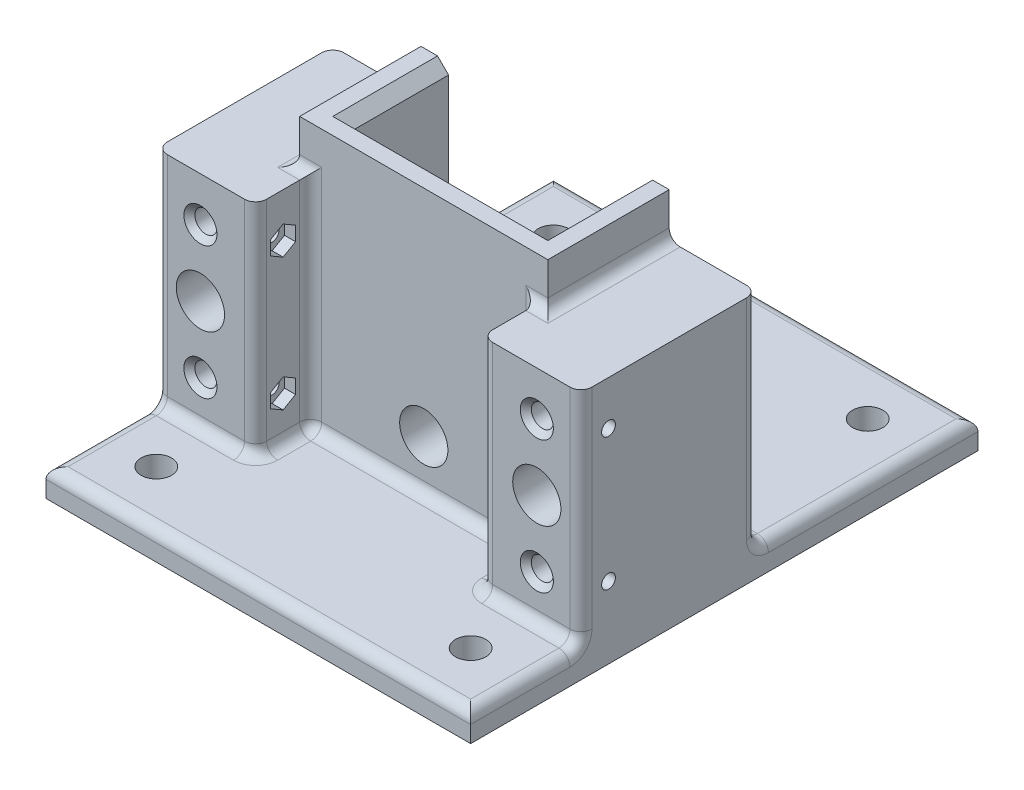
SolidWorks part; units mm, degrees
ref_plane "Спереди" through (0, 0, 0) normal (0, 0, 1) x (1, 0, 0)
ref_plane "Сверху" through (0, 0, 0) normal (0, 1, 0) x (1, 0, 0)
ref_plane "Справа" through (0, 0, 0) normal (1, 0, 0) x (0, 0, -1)
sketch "Эскиз1" plane through (0, 0, 0) normal (0, 1, 0) x (1, 0, 0)
  line L0 (0, 0) -> (0, 22)
  line L1 (0, 0) -> (45, 0)
  line L2 (22.5, 0) -> (22.5, 22) construction
  line L3 (5, 22) -> (40, 22) construction
  line L4 (0, 22) -> (5, 22)
  line L5 (5, 22) -> (5, 5)
  line L6 (5, 5) -> (40, 5)
  line L7 (40, 22) -> (40, 5)
  line L8 (45, 22) -> (40, 22)
  line L9 (45, 0) -> (45, 22)
  point P7 (22.5, 5)
  dimension "D1" = 5
  dimension "D2" = 17.5
  dimension "D3" = 17
  dimension "D4" = 5
extrude "Бобышка-Вытянуть1" add sketch "Эскиз1" along normal blind 30
sketch "Эскиз2" plane through (45, 0, 0) normal (1, 0, 0) x (0, 0, -1)
  line L0 (0, 22) -> (-10, 22)
  line L1 (0, 22) -> (0, -18)
  line L2 (-10, 22) -> (-10, -18)
  line L3 (0, -18) -> (-10, -18)
  line L4 (0, 30) -> (0, 0) construction
  line L5 (0, 30) -> (22, 30) construction
  dimension "D1" = 10
  dimension "D2" = 8
  dimension "D3" = 40
extrude "Бобышка-Вытянуть2" add sketch "Эскиз2" against normal blind 2
sketch "Эскиз3" plane through (45, 0, 0) normal (1, 0, 0) x (0, 0, -1)
  line L0 (0, 22) -> (-10, 22) construction
  line L1 (-10, 22) -> (-10, -18) construction
  line L2 (22, 22) -> (-10, 22)
  line L3 (-10, 22) -> (-10, -18)
  line L4 (-10, -18) -> (0, -18) construction
  line L5 (-10, -18) -> (22, -18)
  line L6 (22, 30) -> (22, 0) construction
  line L7 (22, 22) -> (22, -18)
extrude "Бобышка-Вытянуть3" add sketch "Эскиз3" along normal blind 16
sketch "Эскиз4" plane through (0, 0, -22) normal (0, 0, -1) x (-1, 0, 0)
  line L0 (-53, 22) -> (-53, -18) construction
  line L1 (-61, 22) -> (-45, 22) construction
  line L2 (-61, -18) -> (-45, -18) construction
  circle A0 centre (-53, 2) radius 4.375
  dimension "D1" = 8.75
extrude "Вырез-Вытянуть1" cut sketch "Эскиз4" against normal through all
sketch "Эскиз5" plane through (43, 0, 0) normal (-1, 0, 0) x (0, 0, 1)
  line L0 (5, 22) -> (5, -18) construction
  line L1 (0, 22) -> (10, 22) construction
  line L2 (10, -18) -> (0, -18) construction
  line L3 (5, 2) -> (10, 2) construction
  line L4 (10, 22) -> (10, -18) construction
  circle A0 centre (5, 14) radius 1.25
  circle A1 centre (5, -10) radius 1.25
  dimension "D1" = 12
  dimension "D2" = 2.5
extrude "Вырез-Вытянуть2" cut sketch "Эскиз5" against normal through all
sketch "Эскиз6" plane through (0, 0, -22) normal (0, 0, -1) x (-1, 0, 0)
  line L0 (-61, 15.25) -> (-61, 12.75) construction
  line L1 (-61, 15.25) -> (-61, 12.75) construction
  line L2 (-61, 14) -> (-40, 14) construction
  line L3 (-40, 30) -> (-40, 0) construction
  line L4 (-61, -8.75) -> (-61, -11.25) construction
  line L5 (-61, -8.75) -> (-61, -11.25) construction
  line L6 (-61, -10) -> (-40, -10) construction
  line L7 (-53, 14) -> (-53, -10) construction
  circle A0 centre (-53, 2) radius 4.375 construction
  circle A1 centre (-53, 2) radius 4.375 construction
  circle A2 centre (-53, 14) radius 2
  circle A3 centre (-53, -10) radius 2
  dimension "D1" = 4
  dimension "D2" = 4
extrude "Вырез-Вытянуть3" cut sketch "Эскиз6" against normal through all
sketch "Эскиз7" plane through (43, 0, 0) normal (-1, 0, 0) x (0, 0, 1)
  line L0 (5, 14) -> (5, 16.5981) construction
  line L1 (5, 11.4019) -> (7.25, 12.701)
  line L2 (7.25, 12.701) -> (7.25, 15.299)
  line L3 (7.25, 15.299) -> (5, 16.5981)
  line L4 (5, 16.5981) -> (2.75, 15.299)
  line L5 (2.75, 15.299) -> (2.75, 12.701)
  line L6 (2.75, 12.701) -> (5, 11.4019)
  line L7 (5, -7.4019) -> (2.75, -8.701)
  line L8 (2.75, -8.701) -> (2.75, -11.299)
  line L9 (2.75, -11.299) -> (5, -12.5981)
  line L10 (5, -12.5981) -> (7.25, -11.299)
  line L11 (7.25, -11.299) -> (7.25, -8.701)
  line L12 (7.25, -8.701) -> (5, -7.4019)
  line L13 (5, -10) -> (5, -7.4019) construction
  circle A0 centre (5, 14) radius 1.25 construction
  circle A1 centre (5, -10) radius 1.25 construction
  circle A2 centre (5, 14) radius 1.25 construction
  circle A3 centre (5, -10) radius 1.25 construction
  circle A4 centre (5, 14) radius 2.25 construction
  circle A5 centre (5, -10) radius 2.25 construction
  dimension "D1" = 4.5
  dimension "D2" = 4.5
extrude "Вырез-Вытянуть4" cut sketch "Эскиз7" against normal blind 2
chamfer "Фаска2" distance 3 angle 45 1 edges at (48.625, 2, -22)
chamfer "Фаска3" distance 1 angle 45 2 edges at (51, -10, -22) (51, 14, -22)
sketch "Эскиз8" plane through (0, 0, -5) normal (0, 0, -1) x (-1, 0, 0)
  line L0 (-22.5, 30) -> (-22.5, 0) construction
  line L1 (-40, 30) -> (-5, 30) construction
  line L2 (-40, 0) -> (-5, 0) construction
ref_plane "Sym" through (22.5, 0, 0) normal (1, 0, 0) x (0, -1, 0)
mirror "Зеркальное отражение2" about plane through (22.5, 0, 0) normal (1, 0, 0) of "Вырез-Вытянуть1", "Бобышка-Вытянуть3", "Бобышка-Вытянуть2", "Вырез-Вытянуть4", "Вырез-Вытянуть3", "Вырез-Вытянуть2"
chamfer "Фаска4" distance 3 angle 45 1 edges at (-3.625, 2, -22)
sketch "Эскиз9" plane through (0, 0, 0) normal (0, -1, 0) x (1, 0, 0)
  line L9 (2, 0) -> (0, 0)
  line L10 (2, 0) -> (0, 0)
  line L12 (0, -22) -> (5, -22)
  line L13 (5, -22) -> (5, -5)
  line L14 (5, -5) -> (40, -5)
  line L15 (40, -5) -> (40, -22)
  line L16 (40, -22) -> (45, -22)
  line L17 (45, -22) -> (45, 0)
  line L18 (45, 0) -> (43, 0)
  line L19 (43, 0) -> (2, 0)
  line L20 (0, 0) -> (0, -22)
  line L21 (0, 0) -> (0, -22)
  line L22 (0, -22) -> (45, -22)
  line L27 (45, -22) -> (45, 0)
  line L28 (45, 0) -> (43, 0)
  line L29 (43, 0) -> (2, 0)
  dimension "D1" = 0
extrude "Бобышка-Вытянуть4" add sketch "Эскиз9" along normal up to surface (18 mm away) up to face at (49.5, -18, -2.1667)
sketch "Эскиз10" plane through (0, 0, -22) normal (0, 0, -1) x (-1, 0, 0)
  line L0 (-22.5, 0) -> (-22.5, -18) construction
  line L1 (-5, 0) -> (-40, 0) construction
  line L2 (-61, -18) -> (16, -18) construction
  circle A0 centre (-22.5, -9) radius 4.375
  circle A1 centre (8, 2) radius 4.375 construction
extrude "Вырез-Вытянуть5" cut sketch "Эскиз10" against normal through all
chamfer "Фаска6" distance 3 angle 45 1 edges at (18.125, -9, -22)
sketch "Эскиз11" plane through (0, 0, 10) normal (0, 0, 1) x (1, 0, 0)
  line L0 (53, 16) -> (53, -12) construction
  circle A0 centre (53, 14) radius 2 construction
  circle A1 centre (53, -10) radius 2 construction
ref_plane "Плоскость1" through (53, 0, 0) normal (-1, 0, 0) x (0, -1, 0)
chamfer "Фаска7" distance 1 angle 45 4 edges at (-6, -10, 10) (-6, 14, 10) (51, -10, 10) (51, 14, 10)
chamfer "Фаска8" distance 2 angle 45 1 edges at (5, 30, -13.5)
fillet "Скругление3" radius 2 6 edges at (43, 2, 0) (2, 2, 0)
sketch "Эскиз12" plane through (0, -18, 0) normal (0, -1, 0) x (1, 0, 0)
  line L0 (-16, 10) -> (61, 10)
  line L1 (-16, 10) -> (-16, -62)
  line L2 (61, 10) -> (61, -62)
  line L3 (-16, -62) -> (61, -62)
  line L4 (-16, 10) -> (-16, -22) construction
  line L5 (61, 10) -> (61, -22) construction
  line L6 (61, -22) -> (-16, -22) construction
  line L8 (43, 10) -> (61, 10) construction
  dimension "D1" = 40
extrude "Бобышка-Вытянуть5" add sketch "Эскиз12" along normal blind 5
fillet "Скругление7" radius 2 1 edges
sketch "Эскиз13" plane through (0, 0, 10) normal (0, 0, 1) x (1, 0, 0)
  line L0 (-16, 22) -> (-16, -23) construction
  line L1 (61, -23) -> (-16, -23) construction
  line L2 (61, 22) -> (61, -23) construction
  line L3 (43, -18) -> (2, -18) construction
  line L4 (-16, -18) -> (-16, -23)
  line L5 (61, -23) -> (-16, -23)
  line L6 (61, -18) -> (61, -23)
  line L7 (61, -18) -> (-16, -18)
extrude "Бобышка-Вытянуть6" add sketch "Эскиз13" along normal blind 20
fillet "Скругление10" radius 2 14 edges at (2.5858, -18, 0.5858) (22.5, -18, 0) (42.4142, -18, 0.5858) (22.5, -18, 30)
fillet "Скругление11" radius 2 7 edges at (61, -17.4142, -22.5858) (-16, -17.4142, -22.5858) (22.5, -18, -62)
sketch "Эскиз14" plane through (0, -18, 0) normal (0, 1, 0) x (1, 0, 0)
  line L0 (-14, -20) -> (59, -20) construction
  line L1 (-14, -12) -> (-14, -28) construction
  line L2 (59, -28) -> (59, -12) construction
  line L3 (-14, 52) -> (59, 52) construction
  line L4 (-14, 60) -> (-14, 24) construction
  line L5 (59, 24) -> (59, 60) construction
  line L6 (61, -30) -> (-16, -30) construction
  line L8 (-16, 62) -> (61, 62) construction
  line L9 (-6, -20) -> (-6, 52) construction
  line L10 (22.5, -20) -> (22.5, 52) construction
  line L11 (-16, -30) -> (-16, -12) construction
  circle A0 centre (-6, -20) radius 2.75
  circle A1 centre (51, -20) radius 2.75
  circle A2 centre (-6, 52) radius 2.75
  circle A3 centre (51, 52) radius 2.75
  dimension "D3" = 5.5
  dimension "D1" = 10
  dimension "D2" = 10
  dimension "D4" = 10
extrude "Вырез-Вытянуть6" cut sketch "Эскиз14" against normal through all
chamfer "Фаска9" distance 1 angle 45 2 edges at (-6, -10, -22) (-6, 14, -22)
chamfer "Фаска10" distance 2 angle 45 2 edges at (40, 30, -13.5) (21.5, 30, -5)
